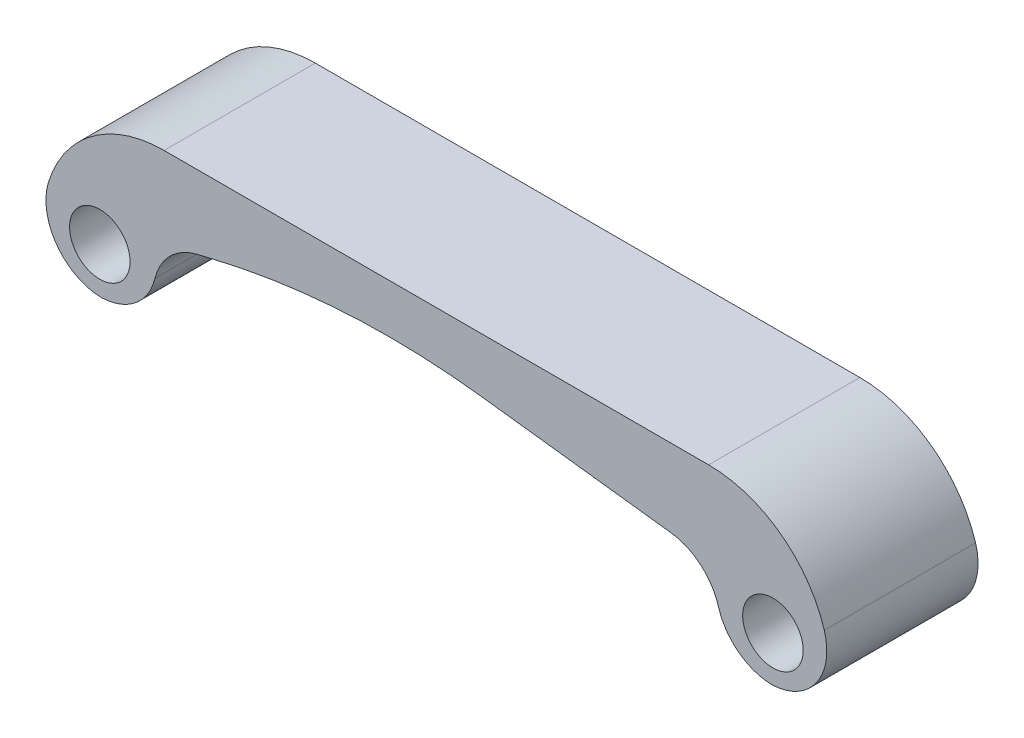
SolidWorks part; units mm, degrees
ref_plane "Front Plane" through (0, 0, 0) normal (0, 0, 1) x (1, 0, 0)
ref_plane "Top Plane" through (0, 0, 0) normal (0, 1, 0) x (1, 0, 0)
ref_plane "Right Plane" through (0, 0, 0) normal (1, 0, 0) x (0, 0, -1)
sketch "Sketch1" plane through (0, 0, 0) normal (0, 0, 1) x (1, 0, 0)
  line L0 (0, 0) -> (-7.5, 0)
  line L1 (-7.5, 0) -> (-7.5, 8)
  line L2 (-7.5, 8) -> (44.5, 8) construction
  line L3 (44.5, 8) -> (44.5, 0)
  line L4 (44.5, 0) -> (37, 0)
  line L5 (37, 0) -> (37, 5)
  line L6 (37, 5) -> (0, 5) construction
  line L7 (0, 5) -> (0, 0)
  line L8 (0, 5) -> (12.5, 8)
  line L9 (12.5, 8) -> (37, 5)
  line L10 (-7.5, 8) -> (-7.5, 10.5)
  line L11 (-7.5, 10.5) -> (44.5, 10.5)
  line L12 (44.5, 10.5) -> (44.5, 8)
  circle A0 centre (-3.75, 3) radius 2
  circle A1 centre (40.75, 3) radius 2
  point P14 (-3.75, 0)
  point P16 (40.75, 0)
  dimension "D1" = 4
  dimension "D2" = 5
  dimension "D3" = 3
  dimension "D4" = 7.5
  dimension "D5" = 7.5
  dimension "D6" = 44.5
  dimension "D7" = 3
  dimension "D8" = 12.5
  dimension "D9" = 2.5
extrude "Boss-Extrude1" add sketch "Sketch1" along normal mid plane 10
fillet "Fillet1" radius 50 1 edges at (12.5, 8, 0)
fillet "Fillet2" radius 8 2 edges at (-7.5, 10.5, 0) (44.5, 10.5, 0)
fillet "Fillet3" radius 3.75 4 edges at (44.5, 0, 0) (37, 0, 0) (-7.5, 0, 0) (0, 0, 0)
fillet "Fillet4" radius 3.75 2 edges at (0, 5, 0) (37, 5, 0)
